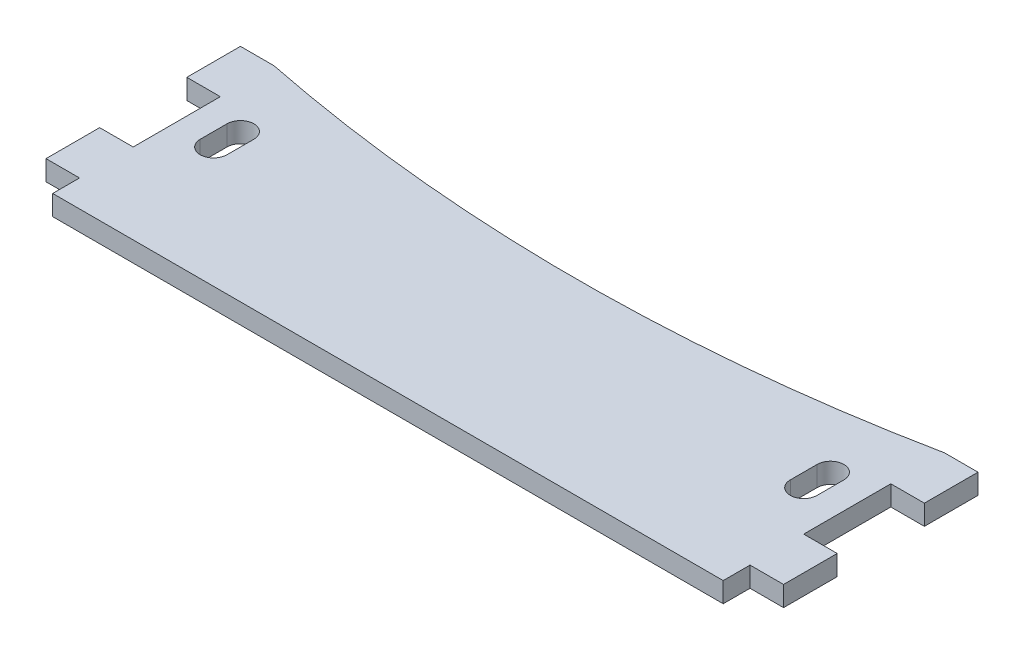
SolidWorks part; units mm, degrees
ref_plane "Front Plane" through (0, 0, 0) normal (0, 0, 1) x (1, 0, 0)
ref_plane "Top Plane" through (0, 0, 0) normal (0, 1, 0) x (1, 0, 0)
ref_plane "Right Plane" through (0, 0, 0) normal (1, 0, 0) x (0, 0, -1)
sketch "Sketch1" plane through (0, 0, 0) normal (0, 1, 0) x (1, 0, 0)
  line L0 (0, 28) -> (0, 0) construction
  line L1 (0, 28) -> (55, 28) construction
  line L2 (55, 33) -> (55, 25)
  line L3 (55, 4) -> (50, 4)
  line L4 (50, 33) -> (55, 33)
  line L5 (46, 22) -> (46, 18)
  line L6 (42, 22) -> (42, 18)
  line L7 (-42, 22) -> (-42, 18)
  line L8 (-46, 22) -> (-46, 18)
  line L9 (-50, 4) -> (-50, 0)
  line L10 (-55, 4) -> (-50, 4)
  line L11 (55, 25) -> (50, 25)
  line L12 (50, 25) -> (50, 12)
  line L13 (50, 12) -> (55, 12)
  line L14 (55, 12) -> (55, 4)
  line L15 (50, 4) -> (50, 0)
  line L16 (50, 0) -> (-50, 0)
  line L17 (-55, 12) -> (-55, 4)
  line L18 (-50, 12) -> (-55, 12)
  line L19 (-50, 25) -> (-50, 12)
  line L20 (-55, 25) -> (-50, 25)
  line L21 (-55, 33) -> (-55, 25)
  line L22 (-50, 33) -> (-55, 33)
  arc A0 (50, 33) -> (-50, 33) centre (0, 280.5) cw
  arc A1 (46, 22) -> (42, 22) centre (44, 22) ccw
  arc A2 (42, 18) -> (46, 18) centre (44, 18) ccw
  arc A3 (-42, 18) -> (-46, 18) centre (-44, 18) cw
  arc A4 (-46, 22) -> (-42, 22) centre (-44, 22) cw
  dimension "D5" = 2
  dimension "D8" = 18
  dimension "D7" = 42
  dimension "D1" = 5
  dimension "D2" = 4
  dimension "D3" = 13
  dimension "D4" = 5
  dimension "D6" = 4
  dimension "D9" = 8
  dimension "D10" = 8
  dimension "D11" = 55
extrude "Boss-Extrude1" add sketch "Sketch1" along normal blind 3
